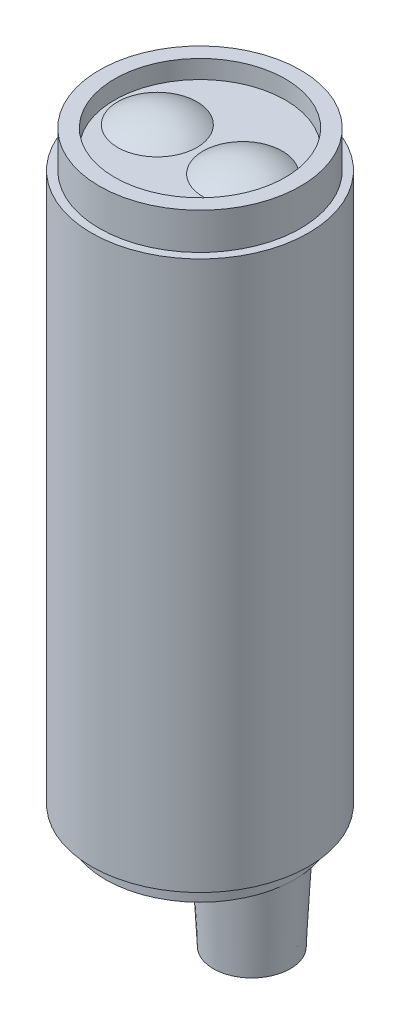
SolidWorks part; units mm, degrees
ref_plane "Front Plane" through (0, 0, 0) normal (0, 0, 1) x (1, 0, 0)
ref_plane "Top Plane" through (0, 0, 0) normal (0, 1, 0) x (1, 0, 0)
ref_plane "Right Plane" through (0, 0, 0) normal (1, 0, 0) x (0, 0, -1)
sketch "Sketch1" plane through (0, 0, 0) normal (0, 1, 0) x (1, 0, 0)
  circle A0 centre (0, 0) radius 8.9
  dimension "D1" = 17.8
extrude "Boss-Extrude1" add sketch "Sketch1" along normal blind 45
sketch "Sketch2" plane through (0, 45, 0) normal (0, 1, 0) x (1, 0, 0)
  circle A0 centre (0, 0) radius 7
  circle A1 centre (0, 0) radius 8.25
  dimension "D1" = 16.5
  dimension "D2" = 14
extrude "Boss-Extrude2" add sketch "Sketch2" along normal blind 3
sketch "Sketch3" plane through (0, 45, 0) normal (0, 1, 0) x (1, 0, 0)
  circle A0 centre (0, 0) radius 7 construction
  circle A1 centre (0, 0) radius 7
extrude "Boss-Extrude3" add sketch "Sketch3" along normal blind 1.5
sketch "Sketch4" plane through (0, 46.5, 0) normal (0, 1, 0) x (1, 0, 0)
  line L0 (-3.5, 0) -> (3.5, 0) construction
  circle A0 centre (-3.5, 0) radius 3.25
  circle A1 centre (3.5, 0) radius 3.25
  point P4 (0, 0)
  dimension "D2" = 6.5
  dimension "D3" = 6.5
  dimension "D1" = 7
sketch "Sketch5" plane through (0, 0, 0) normal (0, 0, 1) x (1, 0, 0)
  line L1 (-3.5, 46.5) -> (-3.5, 47.5)
  line L3 (-3.5, 46.5) -> (-3.5, 47.5) construction
  line L10 (-0.25, 46.5) -> (-6.75, 46.5) construction
  line L11 (-0.25, 46.5) -> (-3.5, 46.5)
  arc A0 (-3.5, 47.5) -> (-0.25, 46.5) centre (-3.5, 41.7188) cw
  dimension "D1" = 1
revolve "Revolve5" add sketch "Sketch5" angle 360 about L3
mirror "Mirror1" about plane through (0, 0, 0) normal (1, 0, 0) of "Revolve5"
sketch "Sketch6" plane through (0, 0, 0) normal (0, -1, 0) x (1, 0, 0)
  circle A0 centre (0, 0) radius 7.75
  dimension "D1" = 15.5
extrude "Boss-Extrude4" add sketch "Sketch6" along normal blind 1.5 separate body
sketch "Sketch7" plane through (0, -1.5, 0) normal (0, -1, 0) x (1, 0, 0)
  circle A0 centre (4.25, 0) radius 3.5
  circle A1 centre (0, 0) radius 7.75 construction
  dimension "D1" = 7
extrude "Boss-Extrude5" add sketch "Sketch7" along normal blind 6.5 draft 3
ref_plane "Plane1" through (0, -10, 0) normal (0, -1, 0) x (-1, 0, 0)
sketch "Sketch8" plane through (0, -10, 0) normal (0, -1, 0) x (-1, 0, 0)
  circle A0 centre (0, 0) radius 8.9 construction
  circle A1 centre (0, 0) radius 8.9
curve "Helix/Spiral1" pitch 0.35 height 56 turns 160
sketch "Sketch10" plane through (0, 0, 0) normal (1, 0, 0) x (0, 0, -1)
  line L0 (9.15, -9.7113) -> (8.65, -10)
  line L1 (8.65, -10) -> (9.15, -10.2887)
  line L2 (9.15, -10.2887) -> (9.15, -9.7113)
  line L3 (8.65, -10) -> (9.15, -10) construction
  point P2 (8.9, -10)
  dimension "D1" = 60
  dimension "D2" = 0.5
sweep "Cut-Sweep1" [suppressed] cut profiles "Sketch10" path "Helix/Spiral1"
